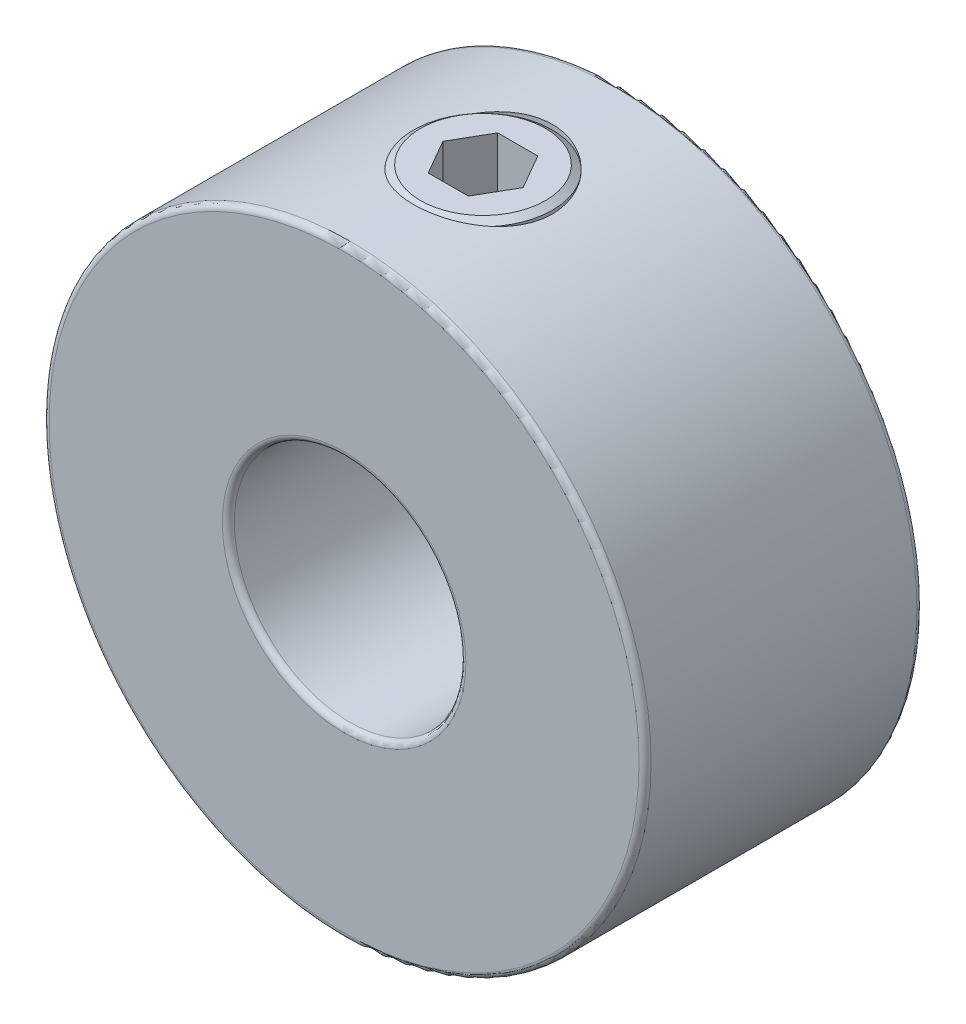
SolidWorks part; units mm, degrees
ref_plane "Front Plane" through (0, 0, 0) normal (0, 0, 1) x (1, 0, 0)
ref_plane "Top Plane" through (0, 0, 0) normal (0, 1, 0) x (1, 0, 0)
ref_plane "Right Plane" through (0, 0, 0) normal (1, 0, 0) x (0, 0, -1)
sketch "Sketch1" plane through (0, 0, 0) normal (0, 0, 1) x (1, 0, 0)
  circle A0 centre (0, 0) radius 6.5
  circle A1 centre (0, 0) radius 2.5
  point P4 (6.5, 0)
  point P5 (0, 6.5)
  dimension "Bore Dia" = 5
  dimension "OD" = 13
extrude "Extrude1" add sketch "Sketch1" along normal blind 6
ref_plane "Plane1" through (0, 6.5, 0) normal (0, 1, 0) x (-1, 0, 0)
sketch "Sketch2" plane through (0, 6.5, 0) normal (0, 1, 0) x (-1, 0, 0)
  line L0 (0, 0) -> (0, 6) construction
  line L2 (6.5, 6) -> (-6.5, 6) construction
  circle A0 centre (0, 3) radius 1.5
  dimension "Set Screw Dia" = 3
extrude "Cut-Extrude1" cut sketch "Sketch2" against normal up to surface (6.5 mm away) up to plane "Top Plane"
ref_plane "Plane2" through (0, 0, 3) normal (0, 0, 1) x (1, 0, 0)
sketch "Sketch3" plane through (0, 0, 3) normal (0, 0, 1) x (1, 0, 0)
  line L0 (-1.35, 6.5) -> (-1.5, 6.395)
  line L1 (0, 3.9939) -> (0, 6.5)
  line L3 (-1.5, 4.1781) -> (-1.5, 6.395)
  line L4 (0, 6.5) -> (-1.35, 6.5)
  line L5 (0, 3.5) -> (0, 0) construction
  line L6 (-1.5, 6.395) -> (0, 6.395) construction
  line L7 (0, 3.9939) -> (-0.8219, 3.5)
  line L8 (-0.8219, 3.5) -> (-1.5, 4.1781)
  point P1 (-0.8219, 3.5)
  dimension "Screw Length" = 3
  dimension "D3" = 3
  dimension "D1" = 2.7
  dimension "D7" = 1.5
  dimension "D2" = 35
  dimension "D4" = 59
  dimension "D5" = 45
revolve "Revolve1" add sketch "Sketch3" angle 360 about L1
sketch "Sketch4" plane through (0, 6.5, 0) normal (0, 1, 0) x (0, 0, -1)
  line L0 (-3, 0.866) -> (-3, -0.866) construction
  line L1 (-3, 0.866) -> (-3.75, 0.433)
  line L2 (-3.75, 0.433) -> (-3.75, -0.433)
  line L3 (-3.75, -0.433) -> (-3, -0.866)
  line L4 (-3, -0.866) -> (-2.25, -0.433)
  line L5 (-2.25, -0.433) -> (-2.25, 0.433)
  line L6 (-2.25, 0.433) -> (-3, 0.866)
  circle A0 centre (-3, 0) radius 0.75 construction
  circle A1 centre (-3, 0) radius 0.866 construction
  dimension "D1" = 1.7321
  dimension "Hex" = 1.5
extrude "Cut-Extrude2" cut sketch "Sketch4" against normal blind 1.2
fillet "Fillet1" radius 0.13 4 edges at (2.5, 0, 0) (2.5, 0, 6) (6.5, 0, 0) (6.5, 0, 6)
ref_plane "Contact Plane 1" through (0, 0, 6) normal (0, 0, 1) x (1, 0, 0)
ref_plane "Contact Plane 2" through (0, 0, 0) normal (0, 0, -1) x (-1, 0, 0)
ref_plane "Contact Plane 3" through (0, 3.5, 0) normal (0, -1, 0) x (-1, 0, 0)
ref_axis "Central Axis 1" through (0, 0, 5.87) along (0, 0, -1)
equation "\"D1@Fillet1\" = \"OD@Sketch1\"*.01"
equation "\"D1@Cut-Extrude2\" = \"Hex@Sketch4\"*.8"
equation "\"D3@Sketch3\"=\"Set Screw Dia@Sketch2\""
equation "\"D1@Sketch3\"=\"Set Screw Dia@Sketch2\"*.9"
